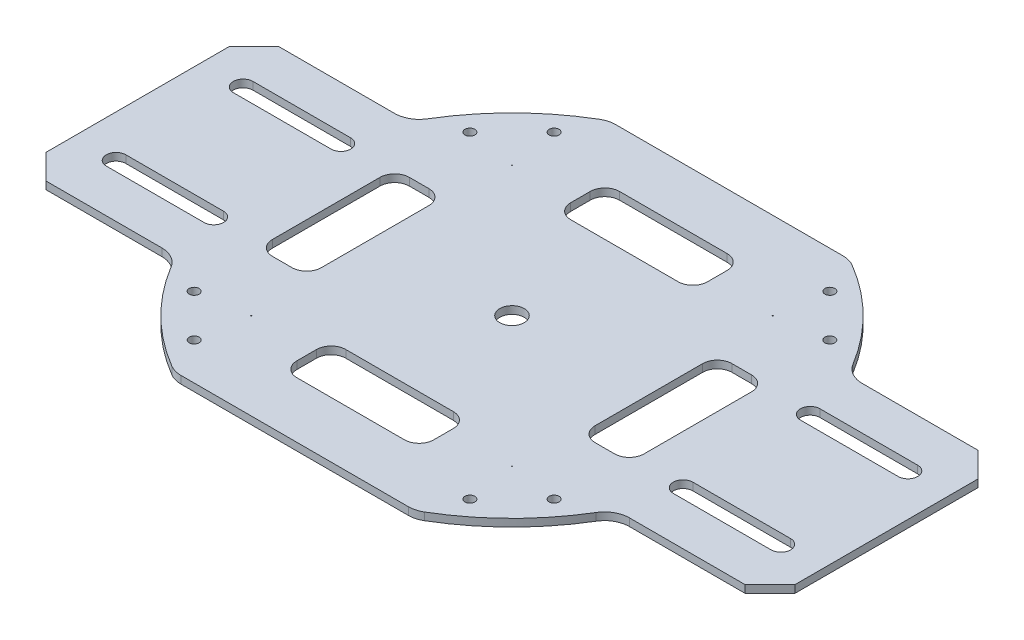
SolidWorks part; units mm, degrees
ref_plane "Front Plane" through (0, 0, 0) normal (0, 0, 1) x (1, 0, 0)
ref_plane "Top Plane" through (0, 0, 0) normal (0, 1, 0) x (1, 0, 0)
ref_plane "Right Plane" through (0, 0, 0) normal (1, 0, 0) x (0, 0, -1)
sketch "Sketch1" plane through (0, 0, 0) normal (0, 1, 0) x (1, 0, 0)
  line L0 (0, -1000) -> (0, 49000) construction
  line L1 (-23.2448, 44.45) -> (23.2448, 44.45)
  line L2 (-76.5969, 18.7325) -> (-76.5969, -18.7325)
  line L3 (-23.2448, -44.45) -> (23.2448, -44.45)
  line L4 (76.5969, 18.7325) -> (76.5969, -18.7325)
  line L6 (35.4178, 36.4243) -> (41.9684, 29.8736) construction
  line L7 (-76.5969, 0) -> (76.5969, 0) construction
  line L8 (-71.5169, 23.8125) -> (-47.8309, 23.8125)
  line L9 (-71.5169, -23.8125) -> (-47.8309, -23.8125)
  line L10 (-23.8125, 64.7529) -> (-23.8125, -44.45) construction
  line L11 (23.8125, 64.7529) -> (23.8125, -44.45) construction
  line L12 (47.8309, -23.8125) -> (71.5169, -23.8125)
  line L13 (47.8309, 23.8125) -> (71.5169, 23.8125)
  line L14 (-76.5969, -18.7325) -> (-71.5169, -23.8125)
  line L15 (-71.5169, 23.8125) -> (-76.5969, 18.7325)
  line L16 (71.5169, 23.8125) -> (76.5969, 18.7325)
  line L17 (71.5169, -23.8125) -> (76.5969, -18.7325)
  line L18 (707.1068, -707.1068) -> (-34648.2323, 34648.2323) construction
  line L19 (-707.1068, -707.1068) -> (34648.2323, 34648.2323) construction
  circle A0 centre (0, 0) radius 2.5
  arc A1 (-25.8276, 43.7444) -> (-43.4827, 26.2659) centre (0, 0) ccw
  arc A2 (25.8276, 43.7444) -> (23.2448, 44.45) centre (23.2448, 39.37) ccw
  arc A3 (-23.2448, 44.45) -> (-25.8276, 43.7444) centre (-23.2448, 39.37) ccw
  arc A4 (25.8276, -43.7444) -> (43.4827, -26.2659) centre (0, 0) ccw
  arc A5 (25.8276, -43.7444) -> (23.2448, -44.45) centre (23.2448, -39.37) cw
  arc A6 (-25.8276, -43.7444) -> (-23.2448, -44.45) centre (-23.2448, -39.37) ccw
  arc A7 (-43.4827, -26.2659) -> (-25.8276, -43.7444) centre (0, 0) ccw
  arc A8 (43.4827, 26.2659) -> (25.8276, 43.7444) centre (0, 0) ccw
  arc A9 (-47.8309, -23.8125) -> (-43.4827, -26.2659) centre (-47.8309, -28.8925) cw
  arc A10 (47.8309, -23.8125) -> (43.4827, -26.2659) centre (47.8309, -28.8925) ccw
  arc A11 (43.4827, 26.2659) -> (47.8309, 23.8125) centre (47.8309, 28.8925) ccw
  arc A12 (-47.8309, 23.8125) -> (-43.4827, 26.2659) centre (-47.8309, 28.8925) ccw
  circle A13 centre (36.8191, 28.198) radius 1.016
  circle A14 centre (28.198, 36.8191) radius 1.016
  circle A15 centre (26.6716, 26.6716) radius 0.081
  circle A16 centre (26.6716, -26.6716) radius 0.081
  circle A17 centre (36.8191, -28.198) radius 1.016
  circle A18 centre (28.198, -36.8191) radius 1.016
  circle A19 centre (-26.6716, -26.6716) radius 0.081
  circle A20 centre (-28.198, -36.8191) radius 1.016
  circle A21 centre (-36.8191, -28.198) radius 1.016
  circle A22 centre (-26.6716, 26.6716) radius 0.081
  circle A23 centre (-36.8191, 28.198) radius 1.016
  circle A24 centre (-28.198, 36.8191) radius 1.016
  point P0 (0, 0)
  point P8 (76.5969, -23.8125)
  point P11 (-76.5969, -23.8125)
  point P12 (-76.5969, 23.8125)
  point P34 (76.5969, 23.8125)
  point P81 (0, 0)
  dimension "D3" = 5
  dimension "D6" = 5.08
  dimension "D1" = 5.08
  dimension "D2" = 5.08
  dimension "D7" = 4.826
  dimension "D4" = 23.8125
  dimension "D5" = 23.8125
  dimension "D8" = 6.096
  dimension "D13" = 4
extrude "Boss-Extrude1" add sketch "Sketch1" along normal blind 1.55
sketch "Sketch2" plane through (0, 1.55, 0) normal (0, 1, 0) x (1, 0, 0)
  line L0 (-76.5969, 0) -> (76.5969, 0) construction
  line L1 (-76.5969, 18.7325) -> (-76.5969, -18.7325) construction
  line L2 (76.5969, -18.7325) -> (76.5969, 18.7325) construction
  line L3 (48, 13) -> (68, 13) construction
  line L4 (48, 15) -> (68, 15)
  line L5 (48, 11) -> (68, 11)
  line L6 (48, -13) -> (68, -13) construction
  line L7 (48, -15) -> (68, -15)
  line L8 (48, -11) -> (68, -11)
  line L9 (0, 44.45) -> (0, -44.45) construction
  line L10 (23.2448, 44.45) -> (-23.2448, 44.45) construction
  line L11 (-23.2448, -44.45) -> (23.2448, -44.45) construction
  line L12 (-48, 13) -> (-68, 13) construction
  line L13 (-48, 15) -> (-68, 15)
  line L14 (-48, 11) -> (-68, 11)
  line L15 (-48, -13) -> (-68, -13) construction
  line L16 (-48, -15) -> (-68, -15)
  line L17 (-48, -11) -> (-68, -11)
  arc A0 (48, 15) -> (48, 11) centre (48, 13) ccw
  arc A1 (68, 11) -> (68, 15) centre (68, 13) ccw
  arc A2 (48, -15) -> (48, -11) centre (48, -13) cw
  arc A3 (68, -11) -> (68, -15) centre (68, -13) cw
  arc A4 (-48, 15) -> (-48, 11) centre (-48, 13) cw
  arc A5 (-68, 11) -> (-68, 15) centre (-68, 13) cw
  arc A6 (-48, -15) -> (-48, -11) centre (-48, -13) ccw
  arc A7 (-68, -11) -> (-68, -15) centre (-68, -13) ccw
  point P8 (58, 13)
  point P15 (58, -13)
  point P20 (46, 13)
  point P21 (70, 13)
  point P33 (-58, 13)
  point P40 (-58, -13)
  dimension "D1" = 11
  dimension "D2" = 15
  dimension "D3" = 26
  dimension "D4" = 46
  dimension "D5" = 70
extrude "Cut-Extrude1" cut sketch "Sketch2" against normal through all
sketch "Sketch3" plane through (0, 1.55, 0) normal (0, 1, 0) x (1, 0, 0)
  line L0 (-76.5969, 0) -> (76.5969, 0) construction
  line L1 (-11, 33) -> (11, 33)
  line L2 (-14, 30) -> (-14, 26)
  line L3 (-11, 23) -> (11, 23)
  line L4 (14, 30) -> (14, 26)
  line L5 (-76.5969, 18.7325) -> (-76.5969, -18.7325) construction
  line L6 (76.5969, -18.7325) -> (76.5969, 18.7325) construction
  line L7 (0, 44.45) -> (0, -44.45) construction
  line L8 (23.2448, 44.45) -> (-23.2448, 44.45) construction
  line L9 (-23.2448, -44.45) -> (23.2448, -44.45) construction
  line L10 (14, -30) -> (14, -26)
  line L11 (-11, -23) -> (11, -23)
  line L12 (-14, -30) -> (-14, -26)
  line L13 (-11, -33) -> (11, -33)
  line L14 (-28, -14) -> (-38, 14) construction
  line L15 (31, 14) -> (35, 14)
  line L16 (28, 11) -> (28, -11)
  line L17 (31, -14) -> (35, -14)
  line L18 (38, 11) -> (38, -11)
  line L19 (28, 14) -> (38, -14) construction
  line L20 (28, -14) -> (38, 14) construction
  line L21 (-28, 14) -> (-38, -14) construction
  line L22 (-38, 11) -> (-38, -11)
  line L23 (-31, -14) -> (-35, -14)
  line L24 (-28, 11) -> (-28, -11)
  line L25 (-31, 14) -> (-35, 14)
  arc A0 (-11, 33) -> (-14, 30) centre (-11, 30) ccw
  arc A1 (-14, 26) -> (-11, 23) centre (-11, 26) ccw
  arc A2 (11, 23) -> (14, 26) centre (11, 26) ccw
  arc A3 (11, 33) -> (14, 30) centre (11, 30) cw
  arc A4 (11, -33) -> (14, -30) centre (11, -30) ccw
  arc A5 (11, -23) -> (14, -26) centre (11, -26) cw
  arc A6 (-14, -26) -> (-11, -23) centre (-11, -26) cw
  arc A7 (-11, -33) -> (-14, -30) centre (-11, -30) cw
  arc A8 (35, -14) -> (38, -11) centre (35, -11) ccw
  arc A9 (28, -11) -> (31, -14) centre (31, -11) ccw
  arc A10 (31, 14) -> (28, 11) centre (31, 11) ccw
  arc A11 (35, 14) -> (38, 11) centre (35, 11) cw
  arc A12 (-35, 14) -> (-38, 11) centre (-35, 11) ccw
  arc A13 (-31, 14) -> (-28, 11) centre (-31, 11) cw
  arc A14 (-28, -11) -> (-31, -14) centre (-31, -11) cw
  arc A15 (-35, -14) -> (-38, -11) centre (-35, -11) cw
  point P36 (33, 0)
  point P69 (-33, 0)
  dimension "D5" = 3
  dimension "D9" = 3
  dimension "D1" = 23
  dimension "D2" = 33
  dimension "D3" = 28
  dimension "D4" = 14
  dimension "D6" = 28
  dimension "D7" = 38
  dimension "D8" = 28
extrude "Cut-Extrude2" cut sketch "Sketch3" against normal through all
